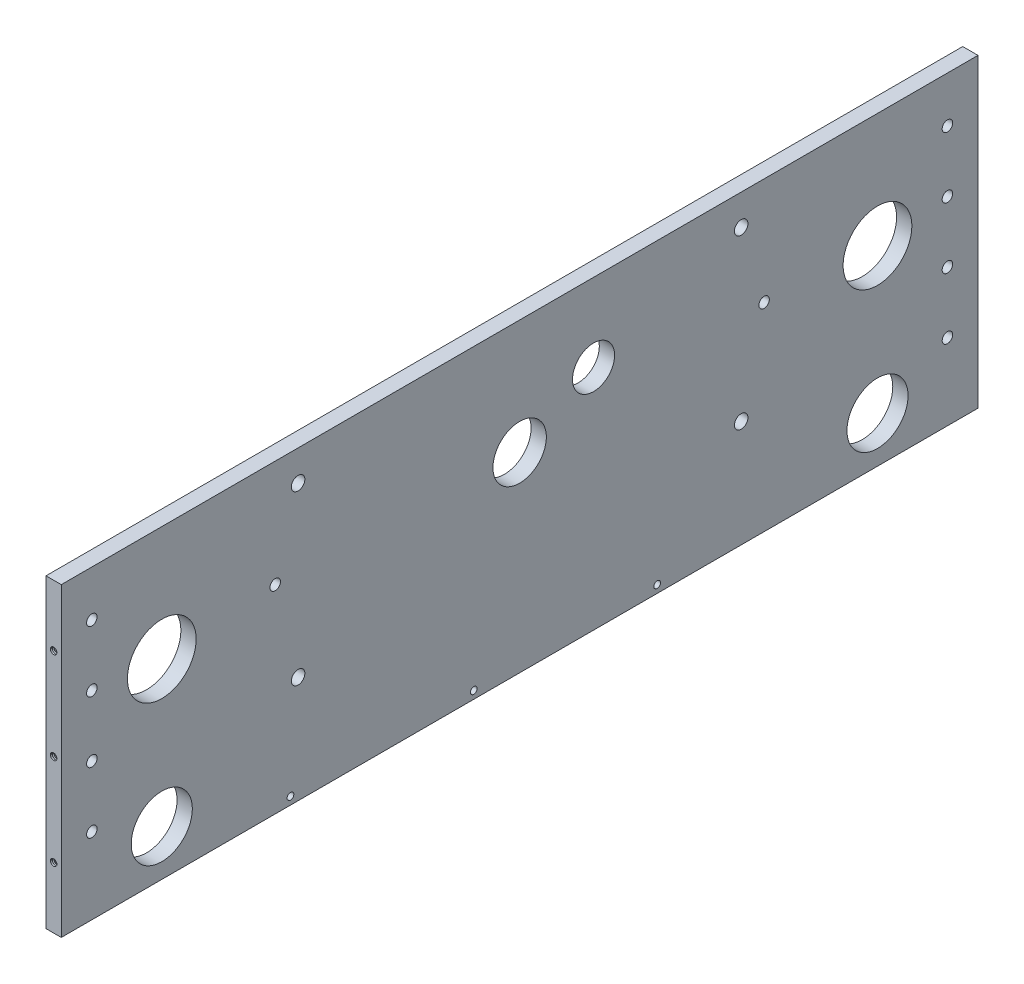
SolidWorks part; units mm, degrees
material "6061-T6 (SS)"
ref_plane "Front Plane" through (0, 0, 0) normal (0, 0, 1) x (1, 0, 0)
ref_plane "Top Plane" through (0, 0, 0) normal (0, 1, 0) x (1, 0, 0)
ref_plane "Right Plane" through (0, 0, 0) normal (1, 0, 0) x (0, 0, -1)
sketch "Sketch1" plane through (0, 0, 0) normal (1, 0, 0) x (0, 0, -1)
  line L1 (-190.5, 63.5) -> (190.5, 63.5)
  line L2 (-190.5, 63.5) -> (-190.5, -63.5)
  line L3 (-190.5, -63.5) -> (190.5, -63.5)
  line L4 (190.5, 63.5) -> (190.5, -63.5)
  line L5 (-190.5, 63.5) -> (190.5, -63.5) construction
  line L6 (-190.5, -63.5) -> (190.5, 63.5) construction
  point P0 (0, 0)
  dimension "D1" = 127
  dimension "D2" = 381
extrude "Boss-Extrude1" add sketch "Sketch1" along normal blind 6.35
sketch "Sketch2" plane through (6.35, 0, 0) normal (1, 0, 0) x (0, 0, -1)
  line L0 (-190.5, -63.5) -> (190.5, -63.5) construction
  line L1 (-148.7297, 15.875) -> (0, 15.875) construction
  line L2 (-74.3648, -34.925) -> (-74.3648, 15.875) construction
  line L3 (0, 15.875) -> (148.7297, 15.875) construction
  line L4 (74.3648, -34.925) -> (74.3648, 15.875) construction
  line L5 (190.5, 63.5) -> (-190.5, 63.5) construction
  line L6 (65.278, 53.34) -> (-56.642, 53.34) construction
  line L7 (65.278, 53.34) -> (65.278, -13.97) construction
  line L8 (65.278, -13.97) -> (-56.642, -13.97) construction
  line L9 (-56.642, 53.34) -> (-56.642, -13.97) construction
  line L10 (-190.5, -63.5) -> (190.5, -63.5) construction
  circle A1 centre (-148.7297, 15.875) radius 14.2875
  circle A2 centre (148.7297, 15.875) radius 14.2875
  circle A3 centre (-148.7297, 15.875) radius 38.1 construction
  circle A4 centre (0, 15.875) radius 38.1 construction
  circle A5 centre (148.7297, 15.875) radius 38.1 construction
  circle A6 centre (-74.3648, -34.925) radius 6.35 construction
  circle A7 centre (74.3648, -34.925) radius 6.35 construction
  circle A8 centre (-74.3648, 9.525) radius 6.35 construction
  circle A9 centre (74.3648, 9.525) radius 6.35 construction
  circle A11 centre (-148.7297, -44.4161) radius 12.7
  circle A12 centre (148.7297, -44.4161) radius 12.7
  circle A13 centre (0, 15.875) radius 29.21 construction
  circle A14 centre (30.7172, 31.115) radius 5.08 construction
  circle A15 centre (30.7172, 31.115) radius 8.75
  circle A16 centre (0, 15.875) radius 11.1125
  point P11 (0, 0)
  dimension "D1" = 28.575
  dimension "D5" = 76.2
  dimension "D7" = 12.7
  dimension "D14" = 25.4
  dimension "D15" = 19.0839
  dimension "D17" = 25.4
  dimension "D20" = 58.42
  dimension "D21" = 10.16
  dimension "D22" = 17.5001
  dimension "D24" = 22.225
  dimension "D25" = 28.575
  dimension "D2" = 79.375
  dimension "D3" = 148.7297
  dimension "D4" = 148.7297
  dimension "D6" = 0
  dimension "D8" = 28.575
  dimension "D9" = 44.45
  dimension "D10" = 56.642
  dimension "D11" = 121.92
  dimension "D12" = 10.16
  dimension "D13" = 49.53
  dimension "D16" = 148.7297
  dimension "D18" = 19.0839
  dimension "D19" = 148.7297
  dimension "D23" = 15.24
extrude "Cut-Extrude1" cut sketch "Sketch2" against normal through all
sketch "Sketch3" plane through (6.35, 0, 0) normal (1, 0, 0) x (0, 0, -1)
  line L0 (-184.404, 19.05) -> (-184.404, -19.05) construction
  line L1 (-190.5, 63.5) -> (-190.5, -63.5) construction
  point P2 (-184.404, 0)
  point P3 (-190.5, 0)
  dimension "D1" = 38.1
  dimension "D2" = 6.096
sketch "Sketch24" plane through (0, 0, 0) normal (-1, 0, 0) x (0, 0, 1)
  line L0 (-190.5, -63.5) -> (-190.5, 63.5) construction
  line L1 (-190.5, 63.5) -> (190.5, 63.5) construction
  point P0 (-92.075, -19.05)
  point P1 (-92.075, 50.8)
  point P2 (92.075, -19.05)
  point P4 (92.075, 50.8)
  dimension "D1" = 12.7
  dimension "D2" = 98.425
  dimension "D3" = 184.15
  dimension "D4" = 12.7
  dimension "D5" = 69.85
  dimension "D6" = 69.85
hole_wizard "CSK for #10 Flat Head Machine Screw2" positions "Sketch25" profile "Sketch26" countersink size "#10" standard "ANSI Inch" end condition through all
sketch "Sketch25" plane through (0, 0, 0) normal (-1, 0, 0) x (0, 0, 1)
  point P0 (-92.075, 50.8)
  point P3 (-92.075, -19.05)
  point P6 (92.075, -19.05)
  point P9 (92.075, 50.8)
sketch "Sketch26" plane through (0, 50.8, -92.075) normal (0, 1, 0) x (0, 0, 1)
  line L0 (0, 0) -> (0, 6.35)
  line L1 (0, 6.35) -> (2.8067, 6.35)
  line L2 (2.8067, 6.35) -> (2.8067, 2.396)
  line L3 (2.8067, 2.396) -> (4.8895, 0)
  line L5 (4.8895, 0) -> (0, 0)
  line L6 (-2.8067, 2.396) -> (-4.8895, 0) construction
  line L11 (0, -6.35) -> (0, 107.95) construction
  dimension "Thru Hole Dia." = 5.6134
  dimension "Thru Hole Depth" = 6.35
  dimension "Near C'Sink Dia." = 9.779
  dimension "Near C'Sink Angle" = 82
sketch "Sketch30" plane through (6.35, 0, 0) normal (1, 0, 0) x (0, 0, -1)
  line L0 (-190.5, -63.5) -> (190.5, -63.5) construction
  line L1 (-190.5, 63.5) -> (-190.5, -63.5) construction
  line L2 (190.5, -63.5) -> (190.5, 63.5) construction
  point P0 (-177.8, -57.15)
  point P1 (-177.8, -31.75)
  point P2 (-177.8, -6.35)
  point P3 (-177.8, 19.05)
  point P4 (-177.8, 44.45)
  point P5 (177.8, -57.15)
  point P6 (177.8, -31.75)
  point P7 (177.8, -6.35)
  point P8 (177.8, 19.05)
  point P9 (177.8, 44.45)
  dimension "D1" = 25.4
  dimension "D2" = 25.4
  dimension "D3" = 25.4
  dimension "D4" = 25.4
  dimension "D5" = 25.4
  dimension "D6" = 25.4
  dimension "D7" = 25.4
  dimension "D8" = 25.4
  dimension "D9" = 6.35
  dimension "D10" = 12.7
  dimension "D11" = 6.35
  dimension "D12" = 12.7
hole_wizard "11/64 (0.17188) Diameter Hole1" positions "Sketch31" profile "Sketch32" hole size "11/64" standard "ANSI Inch" end condition through all
sketch "Sketch31" plane through (6.35, 0, 0) normal (1, 0, 0) x (0, 0, -1)
  point P3 (-177.8, -31.75)
  point P6 (-177.8, -6.35)
  point P9 (-177.8, 19.05)
  point P12 (177.8, 19.05)
  point P15 (177.8, -6.35)
  point P18 (177.8, -31.75)
  point P25 (-177.8, 44.45)
  point P28 (177.8, 44.45)
sketch "Sketch32" plane through (6.35, -31.75, 177.8) normal (0, 1, 0) x (0, 0, -1)
  line L0 (0, 0) -> (0, 6.35)
  line L1 (0, 6.35) -> (2.1829, 6.35)
  line L2 (2.1829, 6.35) -> (2.1829, 0)
  line L5 (2.1829, 0) -> (0, 0)
  line L11 (0, -6.35) -> (0, 107.95) construction
  dimension "Thru Hole Dia." = 4.3658
  dimension "Thru Hole Depth" = 6.35
sketch "Sketch33" plane through (6.35, 0, 0) normal (1, 0, 0) x (0, 0, -1)
  line L1 (-190.5, 63.5) -> (-190.5, -63.5) construction
  line L2 (190.5, 63.5) -> (-190.5, 63.5) construction
  line L3 (190.5, -63.5) -> (190.5, 63.5) construction
  point P0 (-101.6, 19.05)
  point P1 (101.6, 19.05)
  point P6 (0, 0)
  dimension "D1" = 88.9
  dimension "D2" = 88.9
  dimension "D3" = 44.45
hole_wizard "11/64 (0.17188) Diameter Hole2" positions "Sketch34" profile "Sketch35" hole size "11/64" standard "ANSI Inch"
sketch "Sketch34" plane through (6.35, 0, 0) normal (1, 0, 0) x (0, 0, -1)
  point P0 (-101.6, 19.05)
  point P3 (101.6, 19.05)
sketch "Sketch35" plane through (6.35, 19.05, 101.6) normal (0, 1, 0) x (0, 0, -1)
  line L0 (0, 0) -> (0, 10.2016)
  line L1 (0, 10.2016) -> (2.1829, 8.89)
  line L2 (2.1829, 8.89) -> (2.1829, 0)
  line L5 (2.1829, 0) -> (0, 0)
  line L10 (0, 10.2016) -> (-2.1829, 8.89) construction
  line L11 (0, -6.35) -> (0, 107.95) construction
  dimension "Hole Dia." = 4.3658
  dimension "Hole Depth" = 8.89
  dimension "Drill Angle" = 118
sketch "Sketch36" plane through (6.35, 0, 0) normal (1, 0, 0) x (0, 0, -1)
  line L1 (-190.5, -63.5) -> (190.5, -63.5) construction
  line L2 (190.5, -63.5) -> (190.5, 63.5) construction
  point P0 (-95.25, -60.325)
  point P1 (-19.05, -60.325)
  point P2 (57.15, -60.325)
  dimension "D1" = 133.35
  dimension "D2" = 76.2
  dimension "D3" = 76.2
  dimension "D4" = 3.175
hole_wizard "#35 (0.11) Diameter Hole1" positions "Sketch37" profile "Sketch38" hole size "#35" standard "ANSI Inch"
sketch "Sketch37" plane through (6.35, 0, 0) normal (1, 0, 0) x (0, 0, -1)
  point P0 (-95.25, -60.325)
  point P3 (-19.05, -60.325)
  point P6 (57.15, -60.325)
sketch "Sketch38" plane through (6.35, -60.325, 95.25) normal (0, 1, 0) x (0, 0, -1)
  line L0 (0, 0) -> (0, 9.7294)
  line L1 (0, 9.7294) -> (1.397, 8.89)
  line L2 (1.397, 8.89) -> (1.397, 0)
  line L5 (1.397, 0) -> (0, 0)
  line L10 (0, 9.7294) -> (-1.397, 8.89) construction
  line L11 (0, -6.35) -> (0, 107.95) construction
  dimension "Hole Dia." = 2.794
  dimension "Hole Depth" = 8.89
  dimension "Drill Angle" = 118
sketch "Sketch39" plane through (0, 0, 190.5) normal (0, 0, 1) x (1, 0, 0)
  line L0 (6.35, 63.5) -> (0, 63.5) construction
  line L1 (6.35, 63.5) -> (6.35, -63.5) construction
  point P0 (3.175, 38.1)
  point P1 (3.175, 0)
  point P2 (3.175, -38.1)
  dimension "D1" = 25.4
  dimension "D2" = 3.175
hole_wizard "#36 (0.1065) Diameter Hole2" positions "Sketch40" profile "Sketch41" hole size "#36" standard "ANSI Inch"
sketch "Sketch40" plane through (0, 0, 190.5) normal (0, 0, 1) x (1, 0, 0)
  point P0 (3.175, 38.1)
  point P3 (3.175, 0)
  point P6 (3.175, -38.1)
sketch "Sketch41" plane through (3.175, 38.1, 190.5) normal (1, 0, 0) x (0, -1, 0)
  line L0 (0, 0) -> (0, 9.7027)
  line L1 (0, 9.7027) -> (1.3525, 8.89)
  line L2 (1.3525, 8.89) -> (1.3525, 0)
  line L5 (1.3525, 0) -> (0, 0)
  line L10 (0, 9.7027) -> (-1.3525, 8.89) construction
  line L11 (0, -6.35) -> (0, 107.95) construction
  dimension "Hole Dia." = 2.7051
  dimension "Hole Depth" = 8.89
  dimension "Drill Angle" = 118
thread "Thread1" pitch 0.7937 method cut profile "Thread Profile1" start angle 0, offset 0, length 6.35, pitch 0.7937, diameter 2.7051
ref_plane "Plane1" through (1.8225, 38.1, 190.5) normal (0, -1, 0) x (-1, 0, 0)
sketch "Thread Profile1" plane through (1.8225, 38.1, 190.5) normal (0, -1, 0) x (-1, 0, 0)
  line L0 (0, 0) -> (0, 0.7937) construction
  line L1 (0, 0) -> (0.4296, 0.248)
  line L2 (0.4296, 0.248) -> (0.4296, 0.3473)
  line L3 (0.4296, 0.3473) -> (0, 0.5953)
  line L4 (0.4296, 0.2977) -> (0, 0.2977) construction
  line L11 (0, 0) -> (0, 0.5953)
  point P2 (0, 0)
  dimension "Pitch" = 0.7937
  dimension "Profile_Angle" = 60
  dimension "Profile_Land" = 0.0992
  dimension "Profile_Height" = 0.4296
thread "Thread2" pitch 0.7937 method cut profile "Thread Profile2" start angle 0, offset 0, length 6.35, pitch 0.7937, diameter 2.7051
ref_plane "Plane2" through (1.8225, 0, 190.5) normal (0, -1, 0) x (-1, 0, 0)
sketch "Thread Profile2" plane through (1.8225, 0, 190.5) normal (0, -1, 0) x (-1, 0, 0)
  line L0 (0, 0) -> (0, 0.7937) construction
  line L1 (0, 0) -> (0.4296, 0.248)
  line L2 (0.4296, 0.248) -> (0.4296, 0.3473)
  line L3 (0.4296, 0.3473) -> (0, 0.5953)
  line L4 (0.4296, 0.2977) -> (0, 0.2977) construction
  line L11 (0, 0) -> (0, 0.5953)
  point P2 (0, 0)
  dimension "Pitch" = 0.7937
  dimension "Profile_Angle" = 60
  dimension "Profile_Land" = 0.0992
  dimension "Profile_Height" = 0.4296
thread "Thread3" pitch 0.7937 method cut profile "Thread Profile3" start angle 0, offset 0, length 6.35, pitch 0.7937, diameter 2.7051
ref_plane "Plane3" through (1.8225, -38.1, 190.5) normal (0, -1, 0) x (-1, 0, 0)
sketch "Thread Profile3" plane through (1.8225, -38.1, 190.5) normal (0, -1, 0) x (-1, 0, 0)
  line L0 (0, 0) -> (0, 0.7937) construction
  line L1 (0, 0) -> (0.4296, 0.248)
  line L2 (0.4296, 0.248) -> (0.4296, 0.3473)
  line L3 (0.4296, 0.3473) -> (0, 0.5953)
  line L4 (0.4296, 0.2977) -> (0, 0.2977) construction
  line L11 (0, 0) -> (0, 0.5953)
  point P2 (0, 0)
  dimension "Pitch" = 0.7937
  dimension "Profile_Angle" = 60
  dimension "Profile_Land" = 0.0992
  dimension "Profile_Height" = 0.4296
sketch "Sketch48" plane through (0, 0, -190.5) normal (0, 0, -1) x (-1, 0, 0)
  line L0 (-6.35, 63.5) -> (0, 63.5) construction
  line L1 (-6.35, -63.5) -> (-6.35, 63.5) construction
  point P0 (-3.175, 38.1)
  point P1 (-3.175, 0)
  point P2 (-3.175, -38.1)
  dimension "D1" = 25.4
  dimension "D2" = 3.175
  dimension "D3" = 38.1
  dimension "D4" = 38.1
hole_wizard "#36 (0.1065) Diameter Hole3" positions "Sketch49" profile "Sketch50" hole size "#36" standard "ANSI Inch"
sketch "Sketch49" plane through (0, 0, -190.5) normal (0, 0, -1) x (-1, 0, 0)
  point P0 (-3.175, 38.1)
  point P3 (-3.175, 0)
  point P6 (-3.175, -38.1)
sketch "Sketch50" plane through (3.175, 38.1, -190.5) normal (1, 0, 0) x (0, 1, 0)
  line L0 (0, 0) -> (0, 9.7027)
  line L1 (0, 9.7027) -> (1.3525, 8.89)
  line L2 (1.3525, 8.89) -> (1.3525, 0)
  line L5 (1.3525, 0) -> (0, 0)
  line L10 (0, 9.7027) -> (-1.3525, 8.89) construction
  line L11 (0, -6.35) -> (0, 107.95) construction
  dimension "Hole Dia." = 2.7051
  dimension "Hole Depth" = 8.89
  dimension "Drill Angle" = 118
thread "Thread4" pitch 0.7937 method cut profile "Thread Profile4" start angle 0, offset 0, length 6.35, pitch 0.7937, diameter 2.7051
ref_plane "Plane4" through (4.5275, 38.1, -190.5) normal (0, -1, 0) x (1, 0, 0)
sketch "Thread Profile4" plane through (4.5275, 38.1, -190.5) normal (0, -1, 0) x (1, 0, 0)
  line L0 (0, 0) -> (0, 0.7937) construction
  line L1 (0, 0) -> (0.4296, 0.248)
  line L2 (0.4296, 0.248) -> (0.4296, 0.3473)
  line L3 (0.4296, 0.3473) -> (0, 0.5953)
  line L4 (0.4296, 0.2977) -> (0, 0.2977) construction
  line L11 (0, 0) -> (0, 0.5953)
  point P2 (0, 0)
  dimension "Pitch" = 0.7937
  dimension "Profile_Angle" = 60
  dimension "Profile_Land" = 0.0992
  dimension "Profile_Height" = 0.4296
thread "Thread5" pitch 0.7937 method cut profile "Thread Profile5" start angle 0, offset 0, length 6.35, pitch 0.7937, diameter 2.7051
ref_plane "Plane5" through (4.5275, 0, -190.5) normal (0, -1, 0) x (1, 0, 0)
sketch "Thread Profile5" plane through (4.5275, 0, -190.5) normal (0, -1, 0) x (1, 0, 0)
  line L0 (0, 0) -> (0, 0.7937) construction
  line L1 (0, 0) -> (0.4296, 0.248)
  line L2 (0.4296, 0.248) -> (0.4296, 0.3473)
  line L3 (0.4296, 0.3473) -> (0, 0.5953)
  line L4 (0.4296, 0.2977) -> (0, 0.2977) construction
  line L11 (0, 0) -> (0, 0.5953)
  point P2 (0, 0)
  dimension "Pitch" = 0.7937
  dimension "Profile_Angle" = 60
  dimension "Profile_Land" = 0.0992
  dimension "Profile_Height" = 0.4296
thread "Thread6" pitch 0.7937 method cut profile "Thread Profile6" start angle 0, offset 0, length 6.35, pitch 0.7937, diameter 2.7051
ref_plane "Plane6" through (4.5275, -38.1, -190.5) normal (0, -1, 0) x (1, 0, 0)
sketch "Thread Profile6" plane through (4.5275, -38.1, -190.5) normal (0, -1, 0) x (1, 0, 0)
  line L0 (0, 0) -> (0, 0.7937) construction
  line L1 (0, 0) -> (0.4296, 0.248)
  line L2 (0.4296, 0.248) -> (0.4296, 0.3473)
  line L3 (0.4296, 0.3473) -> (0, 0.5953)
  line L4 (0.4296, 0.2977) -> (0, 0.2977) construction
  line L11 (0, 0) -> (0, 0.5953)
  point P2 (0, 0)
  dimension "Pitch" = 0.7937
  dimension "Profile_Angle" = 60
  dimension "Profile_Land" = 0.0992
  dimension "Profile_Height" = 0.4296
